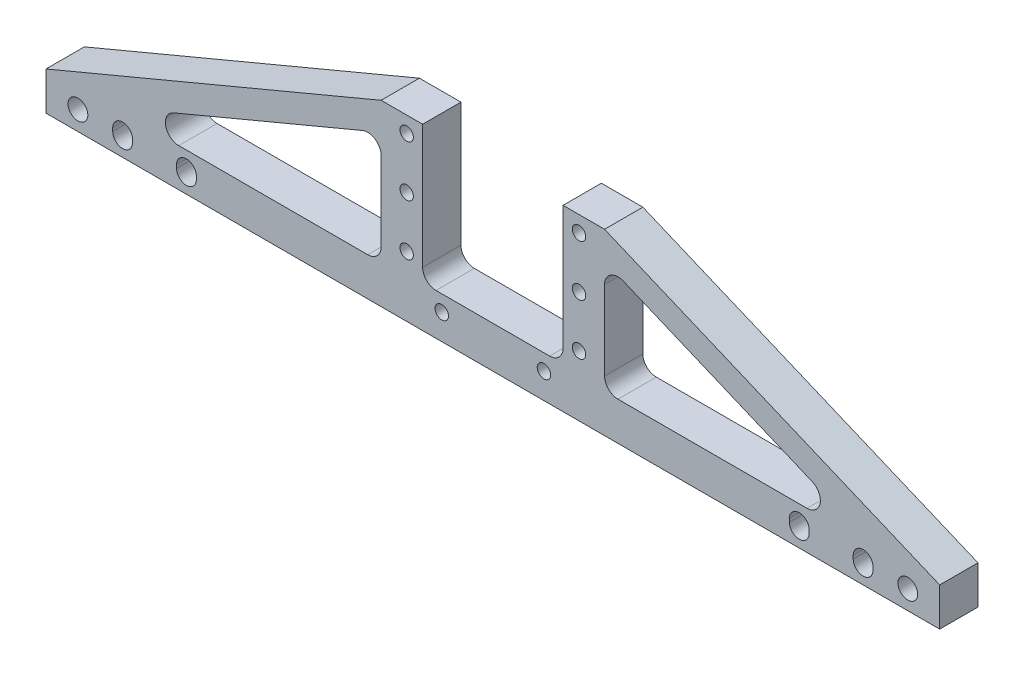
SolidWorks part; units mm, degrees
ref_plane "正面" through (0, 0, 0) normal (0, 0, 1) x (1, 0, 0)
ref_plane "平面" through (0, 0, 0) normal (0, 1, 0) x (1, 0, 0)
ref_plane "右側面" through (0, 0, 0) normal (1, 0, 0) x (0, 0, -1)
sketch "ｽｹｯﾁ1" plane through (0, 0, 0) normal (0, 0, 1) x (1, 0, 0)
  line L0 (-13.5, 21.5) -> (-13.5, 13.5) construction
  line L5 (-13.5, 13.5) -> (-13.5, 5.5) construction
  line L6 (-13.5, 5.5) -> (-13.5, 0) construction
  line L7 (-13.5, 0) -> (-8, 0) construction
  line L8 (-8, 0) -> (8, 0) construction
  line L9 (8, 0) -> (13.5, 0) construction
  line L10 (13.5, 0) -> (13.5, 5.5) construction
  line L11 (13.5, 5.5) -> (13.5, 13.5) construction
  line L12 (13.5, 13.5) -> (13.5, 21.5) construction
  line L13 (-11, 4.6) -> (-11, 24)
  line L14 (-11, 24) -> (-17.5, 24)
  line L15 (-17.5, 24) -> (-17.5, -4) construction
  line L16 (-17.5, -4) -> (17.5, -4)
  line L17 (17.5, -4) -> (17.5, 24) construction
  line L18 (17.5, 24) -> (11, 24)
  line L19 (11, 24) -> (11, 4.6)
  line L20 (8.9, 2.5) -> (-8.9, 2.5)
  line L21 (-17.5, 24) -> (-70, 2)
  line L22 (-70, -4) -> (-17.5, -4)
  line L23 (-17.5, 4.1) -> (-17.5, 16.5061)
  line L24 (-20.4116, 18.4429) -> (-50.017, 6.0368)
  line L25 (-49.2054, 2) -> (-19.6, 2)
  line L26 (-70, 2) -> (-70, -4)
  line L27 (-70, -1) -> (-65, -1) construction
  line L28 (-65, -1) -> (-65, -4) construction
  line L29 (0, -4) -> (0, 24) construction
  line L30 (70, -4) -> (17.5, -4)
  line L31 (70, 2) -> (70, -4)
  line L32 (17.5, 24) -> (70, 2)
  line L33 (20.4116, 18.4429) -> (50.017, 6.0368)
  line L34 (17.5, 4.1) -> (17.5, 16.5061)
  line L35 (49.2054, 2) -> (19.6, 2)
  circle A0 centre (-13.5, 5.5) radius 1.05
  circle A1 centre (-8, 0) radius 1.05
  circle A2 centre (8, 0) radius 1.05
  circle A3 centre (-13.5, 13.5) radius 1.05
  circle A4 centre (-13.5, 21.5) radius 1.05
  circle A5 centre (13.5, 21.5) radius 1.05
  circle A6 centre (13.5, 13.5) radius 1.05
  circle A7 centre (13.5, 5.5) radius 1.05
  arc A8 (-17.5, 4.1) -> (-19.6, 2) centre (-19.6, 4.1) cw
  arc A9 (-50.017, 6.0368) -> (-49.2054, 2) centre (-49.2054, 4.1) ccw
  arc A10 (-17.5, 16.5061) -> (-20.4116, 18.4429) centre (-19.6, 16.5061) ccw
  circle A11 centre (-65, -1) radius 1.55
  circle A12 centre (65, -1) radius 1.55
  arc A13 (17.5, 16.5061) -> (20.4116, 18.4429) centre (19.6, 16.5061) cw
  arc A14 (17.5, 4.1) -> (19.6, 2) centre (19.6, 4.1) ccw
  arc A15 (50.017, 6.0368) -> (49.2054, 2) centre (49.2054, 4.1) cw
  arc A16 (11, 4.6) -> (8.9, 2.5) centre (8.9, 4.6) cw
  arc A17 (-11, 4.6) -> (-8.9, 2.5) centre (-8.9, 4.6) ccw
  point P0 (0, 0)
  point P1 (0, 0)
  point P35 (-17.5, 2)
  point P40 (-17.5, 19.663)
  dimension "D3" = 2.1
  dimension "D15" = 2.1
  dimension "D17" = 3.1
  dimension "D19" = 2.1
  dimension "D1" = 5.5
  dimension "D2" = 8
  dimension "D4" = 27
  dimension "D5" = 2.5
  dimension "D6" = 2.5
  dimension "D7" = 2.5
  dimension "D8" = 4
  dimension "D9" = 4
  dimension "D10" = 2.5
  dimension "D11" = 4
  dimension "D12" = 70
  dimension "D13" = 4
  dimension "D14" = 6
  dimension "D16" = 6
  dimension "D18" = 5
extrude "ﾎﾞｽ - 押し出し1" add sketch "ｽｹｯﾁ1" along normal blind 6
sketch "ｽｹｯﾁ2" plane through (0, 0, 6) normal (0, 0, 1) x (1, 0, 0)
  line L0 (-70, -1) -> (-48, -1) construction
  line L1 (-70, 2) -> (-70, -4) construction
  line L2 (0, -4) -> (0, 2.5) construction
  line L3 (-70, -4) -> (70, -4) construction
  line L4 (8.9, 2.5) -> (-8.9, 2.5) construction
  circle A0 centre (-48, -1) radius 1.55
  circle A1 centre (48, -1) radius 1.55
  circle A2 centre (-58, -1) radius 1.55
  circle A3 centre (58, -1) radius 1.55
  dimension "D1" = 3.1
  dimension "D2" = 22
  dimension "D3" = 10
extrude "ｶｯﾄ - 押し出し1" cut sketch "ｽｹｯﾁ2" against normal blind 3
sketch "ｽｹｯﾁ3" plane through (0, 0, 0) normal (0, 0, -1) x (-1, 0, 0)
  line L0 (-58, -0.75) -> (-58, -1.25) construction
  line L1 (-56.45, -0.75) -> (-56.45, -1.25)
  line L2 (-59.55, -0.75) -> (-59.55, -1.25)
  line L3 (-48, -0.75) -> (-48, -1.25) construction
  line L4 (-46.45, -0.75) -> (-46.45, -1.25)
  line L5 (-49.55, -0.75) -> (-49.55, -1.25)
  line L6 (0, 2.5) -> (0, -4) construction
  line L7 (-8.9, 2.5) -> (8.9, 2.5) construction
  line L8 (70, -4) -> (-70, -4) construction
  line L9 (58, -0.75) -> (58, -1.25) construction
  line L10 (56.45, -0.75) -> (56.45, -1.25)
  line L11 (59.55, -0.75) -> (59.55, -1.25)
  line L12 (48, -0.75) -> (48, -1.25) construction
  line L13 (46.45, -0.75) -> (46.45, -1.25)
  line L14 (49.55, -0.75) -> (49.55, -1.25)
  arc A0 (-56.45, -0.75) -> (-59.55, -0.75) centre (-58, -0.75) ccw
  arc A1 (-59.55, -1.25) -> (-56.45, -1.25) centre (-58, -1.25) ccw
  circle A2 centre (-58, -1) radius 1.55 construction
  arc A3 (-46.45, -0.75) -> (-49.55, -0.75) centre (-48, -0.75) ccw
  arc A4 (-49.55, -1.25) -> (-46.45, -1.25) centre (-48, -1.25) ccw
  arc A5 (56.45, -0.75) -> (59.55, -0.75) centre (58, -0.75) cw
  arc A6 (59.55, -1.25) -> (56.45, -1.25) centre (58, -1.25) cw
  arc A7 (46.45, -0.75) -> (49.55, -0.75) centre (48, -0.75) cw
  arc A8 (49.55, -1.25) -> (46.45, -1.25) centre (48, -1.25) cw
  point P2 (-58, -1)
  point P13 (-48, -1)
  point P25 (58, -1)
  point P32 (48, -1)
  dimension "D1" = 0.5
  dimension "D2" = 2
extrude "ｶｯﾄ - 押し出し2" cut sketch "ｽｹｯﾁ3" against normal through all
